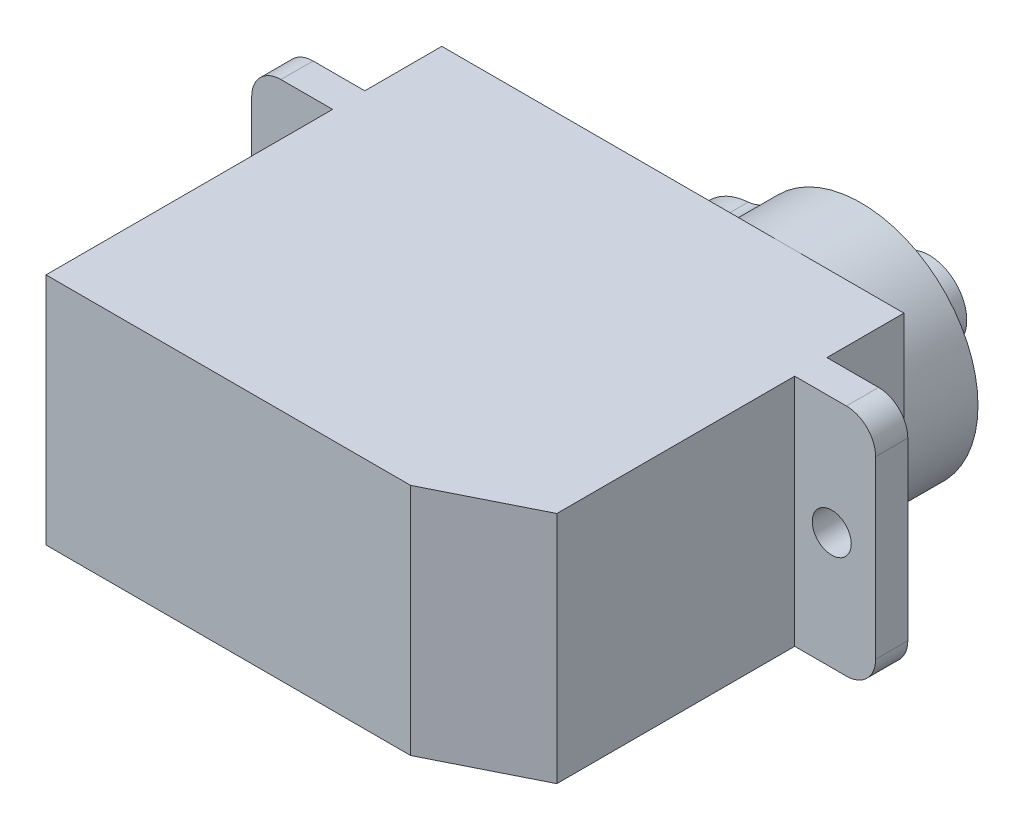
SolidWorks part; units mm, degrees
ref_plane "Front Plane" through (0, 0, 0) normal (0, 0, 1) x (1, 0, 0)
ref_plane "Top Plane" through (0, 0, 0) normal (0, 1, 0) x (1, 0, 0)
ref_plane "Right Plane" through (0, 0, 0) normal (1, 0, 0) x (0, 0, -1)
sketch "Sketch1" plane through (0, 0, 0) normal (0, 1, 0) x (1, 0, 0)
  line L0 (6.85, -10.15) -> (11.85, -7.65)
  line L1 (-11.85, -10.15) -> (11.85, -10.15)
  line L2 (-11.85, -10.15) -> (-11.85, 10.15)
  line L3 (-11.85, 10.15) -> (11.85, 10.15)
  line L4 (11.85, -10.15) -> (11.85, 10.15)
  line L5 (-11.85, -10.15) -> (11.85, 10.15) construction
  line L6 (-11.85, 10.15) -> (11.85, -10.15) construction
  line L7 (-16, 6.2) -> (16, 6.2)
  line L8 (-16, 6.2) -> (-16, 4.55)
  line L9 (-16, 4.55) -> (16, 4.55)
  line L10 (16, 6.2) -> (16, 4.55)
  point P0 (0, 0)
  dimension "D1" = 1.65
  dimension "D2" = 20.3
  dimension "D3" = 23.7
  dimension "D4" = 4.15
  dimension "D5" = 32
  dimension "D6" = 14.7
  dimension "D7" = 5
  dimension "D8" = 2.5
  dimension "D9" = 4.15
  dimension "D10" = 3.95
extrude "Boss-Extrude1" add sketch "Sketch1" along normal blind 6 and the other way blind 6 contours L2 L7 L4 L3 | L2 L9 L4 L7 | L8 L9 L2 L7 | L10 L7 L4 L9 | L9 L2 L1 L0 L4 region at (-0.186, 0, 2.681) region at (0, 0, -5.375) region at (13.925, 0, -5.375) region at (-13.925, 0, -5.375) region at (0, 0, -8.175)
fillet "Fillet1" radius 1.5 4 edges at (16, -6, -5.375) (16, 6, -5.375) (-16, 6, -5.375) (-16, -6, -5.375)
sketch "Sketch2" plane through (0, 0, -6.2) normal (0, 0, -1) x (-1, 0, 0)
  line L0 (-16, 0) -> (16, 0) construction
  line L1 (-16, -4.5) -> (-16, 4.5) construction
  line L2 (16, -4.5) -> (16, 4.5) construction
  line L3 (16, -4.5) -> (16, 4.5) construction
  line L5 (-16, -4.5) -> (-16, 4.5) construction
  line L6 (-11.85, -6) -> (-11.85, 6) construction
  circle A0 centre (-13.75, 0) radius 1
  circle A1 centre (13.75, 0) radius 1
  dimension "D1" = 2
  dimension "D2" = 29.5
  dimension "D4" = 1.25
  dimension "D5" = 1.25
  dimension "D3" = 2.25
  dimension "D6" = 24.6
extrude "Cut-Extrude1" cut sketch "Sketch2" against normal through all
sketch "Sketch3" plane through (0, 0, -10.15) normal (0, 0, -1) x (-1, 0, 0)
  line L0 (-11.85, 0) -> (11.85, 0) construction
  line L1 (-11.85, -6) -> (-11.85, 6) construction
  line L2 (11.85, -6) -> (11.85, 6) construction
  line L3 (11.85, 6) -> (-11.85, 6) construction
  line L5 (11.85, -6) -> (-11.85, -6) construction
  circle A0 centre (-5.85, 0) radius 6
  circle A1 centre (-0.3, 0) radius 3.15
  dimension "D1" = 14.7
  dimension "D2" = 6.3
  dimension "D3" = 12
extrude "Boss-Extrude2" add sketch "Sketch3" along normal blind 3.8 contours A0 L0 A1 | L0 A0 A1 | A1 L0 A0 | L0 A1 A0 | L0 A0 A1 | A0 L0 A1 region at (-1.1108, 1.4189, -10.15) region at (1.5363, -1.265, -10.15) region at (1.5363, 1.265, -10.15) region at (-1.1108, -1.4189, -10.15) region at (6.5928, -2.7671, -10.15) region at (6.5928, 2.7671, -10.15)
fillet "Fillet2" radius 1.5 2 edges at (0.7257, -3.1211, -12.05) (0.7257, 3.1211, -12.05)
sketch "Sketch4" plane through (0, 0, -10.15) normal (0, 0, -1) x (-1, 0, 0)
  line L0 (11.85, -6) -> (11.85, 6) construction
  line L1 (3.85, 5) -> (9.85, 5)
  line L2 (3.85, 5) -> (3.85, -5)
  line L3 (3.85, -5) -> (9.85, -5)
  line L4 (9.85, 5) -> (9.85, -5)
  line L5 (6.85, 5) -> (6.85, 6) construction
  line L6 (11.85, 6) -> (-5.85, 6) construction
  line L7 (6.85, -5) -> (6.85, -6) construction
  line L8 (11.85, -6) -> (-5.85, -6) construction
  dimension "D1" = 6
  dimension "D2" = 10
  dimension "D3" = 2
extrude "Cut-Extrude2" cut sketch "Sketch4" against normal blind 0.2
sketch "Sketch5" plane through (0, 0, -13.95) normal (0, 0, -1) x (-1, 0, 0)
  circle A0 centre (0, 0) radius 1
  dimension "D1" = 2
extrude "Boss-Extrude3" add sketch "Sketch5" along normal blind 0.5
sketch "Sketch6" plane through (0, 0, -13.95) normal (0, 0, -1) x (-1, 0, 0)
  circle A0 centre (-5.85, 0) radius 1.925
  dimension "D1" = 3.85
extrude "Boss-Extrude4" add sketch "Sketch6" along normal blind 0.5
chamfer "Chamfer1" distance 0.5 angle 45 1 edges at (3.925, 0, -13.95)
sketch "Sketch7" plane through (0, 0, -14.45) normal (0, 0, -1) x (-1, 0, 0)
  circle A0 centre (-5.85, 0) radius 1.925
  circle A1 centre (-5.85, 0) radius 1.925 construction
extrude "Boss-Extrude5" add sketch "Sketch7" along normal blind 3
sketch "Sketch8" plane through (0, 0, 0) normal (0, 1, 0) x (1, 0, 0)
  line L0 (5.85, 17.45) -> (5.85, 8.4814) construction
  line L1 (7.775, 17.45) -> (3.925, 17.45) construction
  line L2 (7.775, 14.45) -> (7.775, 17.45) construction
  line L3 (7.85, 14.45) -> (11.2045, 14.45) construction
  line L5 (3.785, 14.45) -> (5.85, 14.45) construction
  line L6 (3.925, 14.45) -> (7.775, 14.45) construction
  line L7 (7.85, 17.0338) -> (7.85, 11.9873) construction
  circle A0 centre (8.025, 14.9184) radius 0.5
  dimension "D1" = 1
  dimension "D2" = 0.25
  dimension "D3" = 2
revolve "Cut-Revolve1" cut sketch "Sketch8" angle 360 about L0
hole_wizard "M2x0.4 Tapped Hole1" positions "Sketch10" profile "Sketch11" tap size "M2x0.4" standard "ANSI Metric"
sketch "Sketch10" plane through (0, 0, -17.45) normal (0, 0, -1) x (-1, 0, 0)
  point P0 (-5.85, 0)
sketch "Sketch11" plane through (5.85, 0, -17.45) normal (1, 0, 0) x (0, 1, 0)
  line L0 (0, 0) -> (0, 5.6807)
  line L1 (0, 5.6807) -> (0.8, 5.2)
  line L2 (0.8, 5.2) -> (0.8, 0)
  line L5 (0.8, 0) -> (0, 0)
  line L10 (0, 5.6807) -> (-0.8, 5.2) construction
  line L11 (0, -6.35) -> (0, 107.95) construction
  dimension "Tap Drill Dia." = 1.6
  dimension "Tap Drill Depth" = 5.2
  dimension "Drill Angle" = 118
cosmetic thread "Hole Thread1" parameters "D1"=4, "D2"=2
